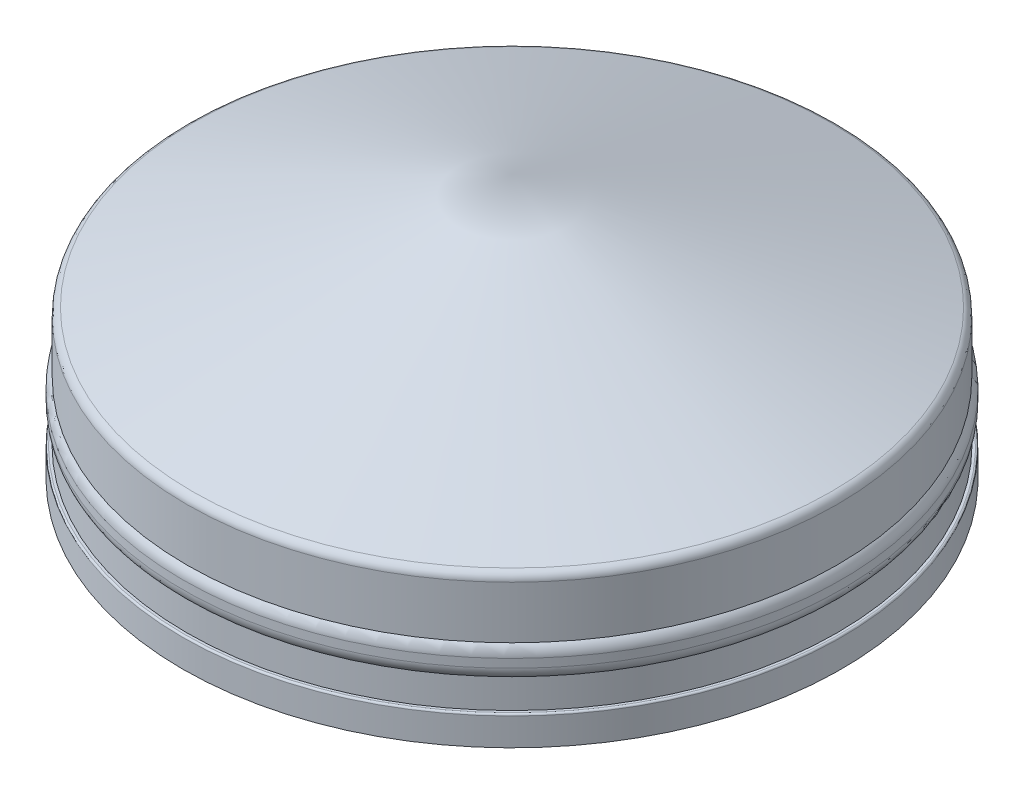
SolidWorks part; units mm, degrees
ref_plane "Front Plane" through (0, 0, 0) normal (0, 0, 1) x (1, 0, 0)
ref_plane "Top Plane" through (0, 0, 0) normal (0, 1, 0) x (1, 0, 0)
ref_plane "Right Plane" through (0, 0, 0) normal (1, 0, 0) x (0, 0, -1)
sketch "Sketch1" plane through (0, 0, 0) normal (0, 1, 0) x (1, 0, 0)
  circle A0 centre (0, 0) radius 11.25
  dimension "D1" = 22.5
extrude "Boss-Extrude1" add sketch "Sketch1" along normal blind 1
sketch "Sketch2" plane through (0, 1, 0) normal (0, 1, 0) x (1, 0, 0)
  circle A0 centre (0, 0) radius 11.105
  dimension "D1" = 22.21
extrude "Boss-Extrude2" add sketch "Sketch2" along normal blind 1
sketch "Sketch3" plane through (0, 2, 0) normal (0, 1, 0) x (1, 0, 0)
  circle A0 centre (0, 0) radius 11.25
  dimension "D1" = 22.5
extrude "Boss-Extrude3" add sketch "Sketch3" along normal blind 1
sketch "Sketch4" plane through (0, 3, 0) normal (0, 1, 0) x (1, 0, 0)
  circle A0 centre (0, 0) radius 11.1
  dimension "D1" = 22.2
extrude "Boss-Extrude4" add sketch "Sketch4" along normal blind 2
sketch "Sketch5" plane through (0, 5, 0) normal (0, 1, 0) x (1, 0, 0)
  line L0 (0, 0) -> (0.6661, -11.08) construction
  circle A0 centre (0, 0) radius 11.1 construction
ref_plane "Plane1" through (0, 0, 0) normal (-0.9982, 0, 0.06) x (0.06, 0, 0.9982)
sketch "Sketch6" plane through (0, 0, 0) normal (-0.9982, 0, 0.06) x (0.06, 0, 0.9982)
  line L0 (0, 5) -> (0, 9)
  line L1 (0, 9) -> (11.1, 5)
  line L2 (11.1, 5) -> (0, 5)
  dimension "D1" = 4
revolve "Revolve1" add sketch "Sketch6" angle 360 about L0 region at (0.222, 6.3333, 3.6933)
fillet "Fillet1" radius 0.3 1 edges at (0, 5, 11.1)
fillet "Fillet3" radius 0.5 2 edges at (0, 2, 11.25) (0, 3, 11.25)
fillet "Fillet4" radius 0.06 1 edges at (0, 1, 11.25)
